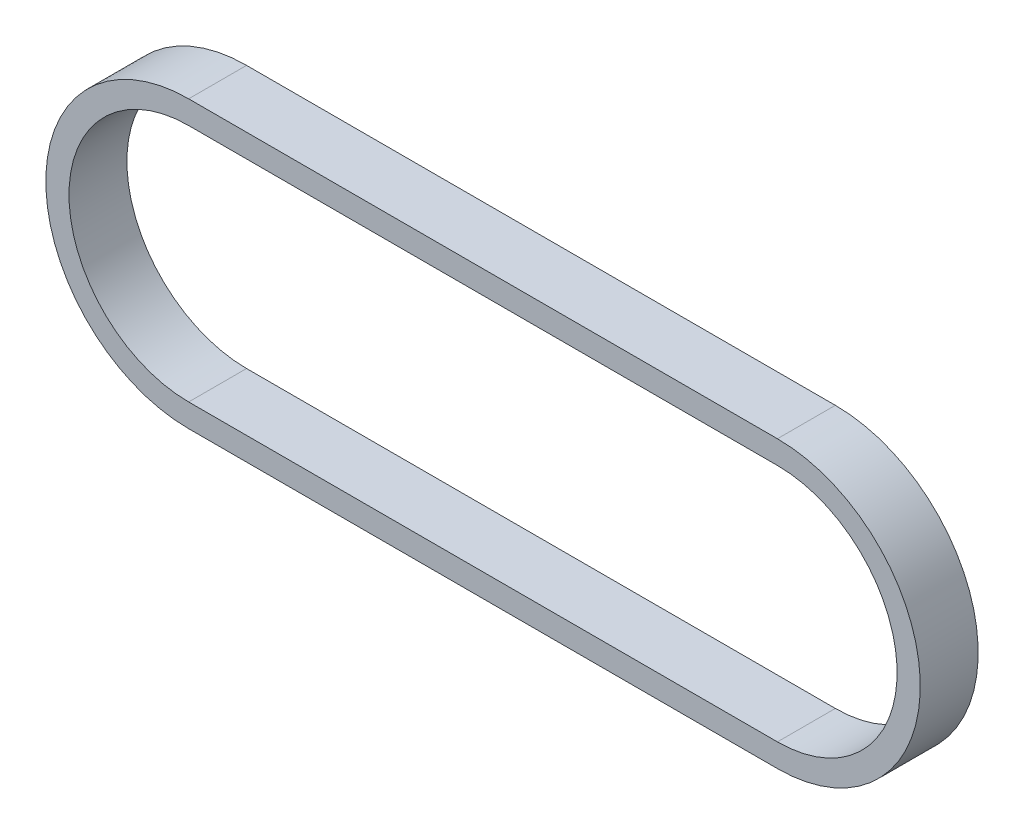
SolidWorks part; units mm, degrees
ref_plane "Plan de face" through (0, 0, 0) normal (0, 0, 1) x (1, 0, 0)
ref_plane "Plan de dessus" through (0, 0, 0) normal (0, 1, 0) x (1, 0, 0)
ref_plane "Plan de droite" through (0, 0, 0) normal (1, 0, 0) x (0, 0, -1)
sketch "Esquisse1" plane through (0, 0, 0) normal (0, 0, 1) x (1, 0, 0)
  line L0 (0, 0) -> (61, 0) construction
  line L1 (0, 12.4) -> (61, 12.4)
  line L2 (0, -12.4) -> (61, -12.4)
  line L3 (0, 0) -> (61, 0) construction
  line L4 (0, 14.8) -> (61, 14.8)
  line L5 (0, -14.8) -> (61, -14.8)
  arc A0 (0, 12.4) -> (0, -12.4) centre (0, 0) ccw
  arc A1 (61, -12.4) -> (61, 12.4) centre (61, 0) ccw
  arc A2 (0, 14.8) -> (0, -14.8) centre (0, 0) ccw
  arc A3 (61, -14.8) -> (61, 14.8) centre (61, 0) ccw
  point P3 (30.5, 0)
  point P10 (30.5, 0)
  dimension "D3" = 12.4
  dimension "D1" = 61
  dimension "D2" = 2.4
extrude "Boss.-Extru.1" add sketch "Esquisse1" along normal blind 6
